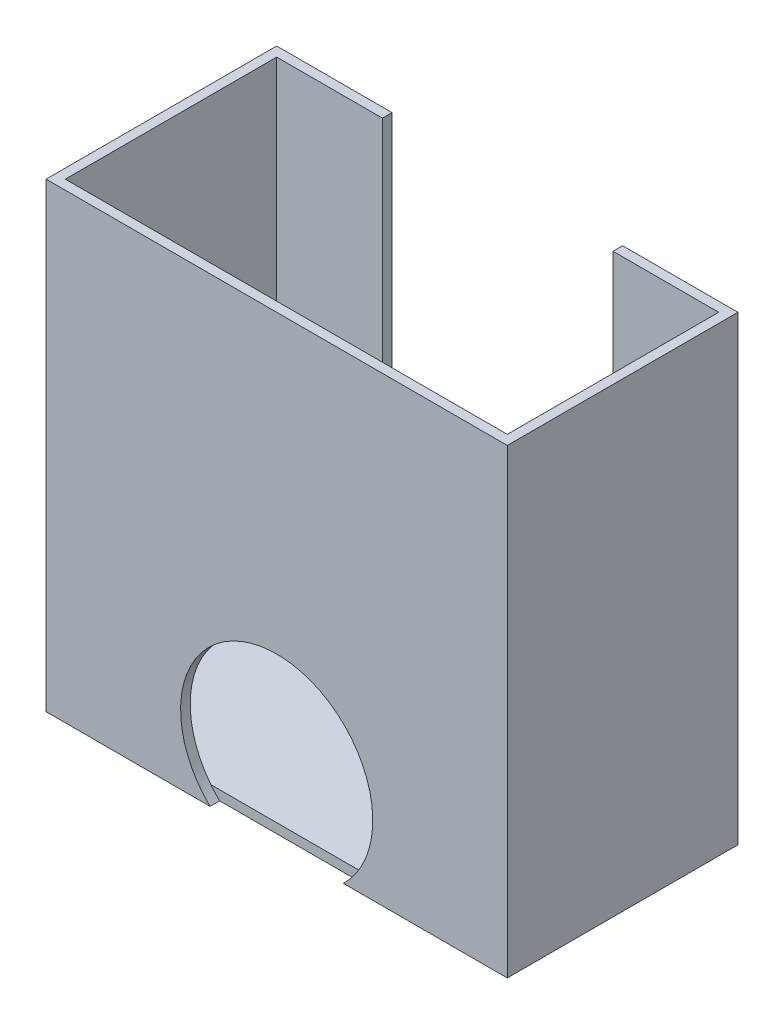
SolidWorks part; units mm, degrees
ref_plane "Front Plane" through (0, 0, 0) normal (0, 0, 1) x (1, 0, 0)
ref_plane "Top Plane" through (0, 0, 0) normal (0, 1, 0) x (1, 0, 0)
ref_plane "Right Plane" through (0, 0, 0) normal (1, 0, 0) x (0, 0, -1)
sketch "Sketch1" plane through (0, 0, 0) normal (0, 1, 0) x (1, 0, 0)
  line L1 (76.2, -38.1) -> (-76.2, -38.1)
  line L2 (76.2, -38.1) -> (76.2, 38.1)
  line L3 (76.2, 38.1) -> (-76.2, 38.1)
  line L4 (-76.2, -38.1) -> (-76.2, 38.1)
  line L5 (76.2, -38.1) -> (-76.2, 38.1) construction
  line L6 (76.2, 38.1) -> (-76.2, -38.1) construction
  point P0 (0, 0)
  dimension "D1" = 152.4
  dimension "D2" = 76.2
extrude "Boss-Extrude1" add sketch "Sketch1" along normal blind 152.4
shell "Shell1" thickness 3.175 removed face at (0, 152.4, 0)
sketch "Sketch2" plane through (0, 0, -38.1) normal (0, 0, -1) x (-1, 0, 0)
  line L0 (-76.2, 0) -> (76.2, 0) construction
  line L3 (-38.1, 0) -> (38.1, 0)
  line L4 (-38.1, 0) -> (-38.1, 152.4)
  line L5 (-38.1, 152.4) -> (38.1, 152.4)
  line L6 (38.1, 0) -> (38.1, 152.4)
  line L7 (-76.2, 152.4) -> (76.2, 152.4) construction
  point P6 (0, 152.4)
  dimension "D1" = 76.2
extrude "Cut-Extrude1 BACK MOUSEHOLE" cut sketch "Sketch2" against normal up to surface (3.175 mm away) up to face at (0, 77.7875, -34.925)
sketch "Sketch3" plane through (0, 0, 38.1) normal (0, 0, 1) x (1, 0, 0)
  circle A0 centre (0, 22.86) radius 31.75
  dimension "D1" = 63.5
  dimension "D2" = 22.86
extrude "Cut-Extrude2" cut sketch "Sketch3" against normal up to surface (3.175 mm away) up to face at (0, 77.7875, 34.925)
sketch "Sketch4" plane through (0, 3.175, 0) normal (0, 1, 0) x (1, 0, 0)
  line L0 (-73.025, 34.925) -> (-73.025, -34.925)
  line L1 (-73.025, -34.925) -> (-39.5001, -34.925)
  line L2 (-73.025, -34.925) -> (73.025, -34.925) construction
  arc A0 (-73.025, 34.925) -> (-39.5001, -34.925) centre (16.5045, 34.925) ccw
extrude "Boss-Extrude2" add sketch "Sketch4" along normal blind 45.72 separate body
equation "\"eighthinch\"= 0.125"
